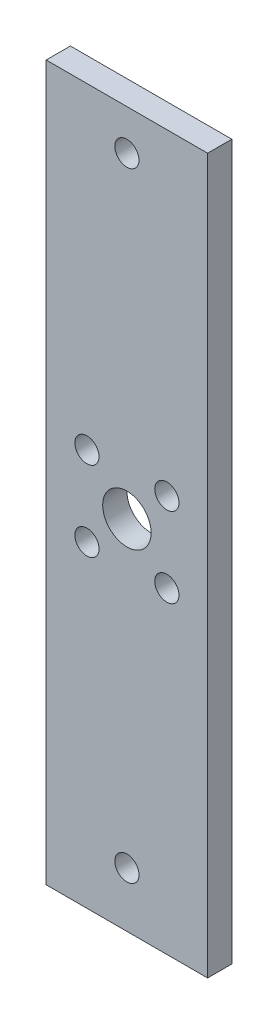
SolidWorks part; units mm, degrees
ref_plane "前视基准面" through (0, 0, 0) normal (0, 0, 1) x (1, 0, 0)
ref_plane "上视基准面" through (0, 0, 0) normal (0, 1, 0) x (1, 0, 0)
ref_plane "右视基准面" through (0, 0, 0) normal (1, 0, 0) x (0, 0, -1)
other "Configuration Table"
sketch "草图1" plane through (0, 0, 0) normal (0, 0, 1) x (1, 0, 0)
  line L1 (85.4719, -52.7604) -> (-85.4719, -52.7604)
  line L2 (85.4719, -52.7604) -> (85.4719, 52.7604)
  line L3 (85.4719, 52.7604) -> (-85.4719, 52.7604)
  line L4 (-85.4719, -52.7604) -> (-85.4719, 52.7604)
  line L5 (85.4719, -52.7604) -> (-85.4719, 52.7604) construction
  line L6 (85.4719, 52.7604) -> (-85.4719, -52.7604) construction
  point P0 (0, 0)
extrude "凸台-拉伸1" add sketch "草图1" along normal blind 3
sketch "草图2" plane through (0, 0, 0) normal (0, 0, -1) x (-1, 0, 0)
  circle A0 centre (7.0546, 5.7109) radius 1.5
  circle A1 centre (16.954, 5.7109) radius 1.5
  circle A2 centre (16.954, -4.1886) radius 1.5
  circle A3 centre (7.0546, -4.1886) radius 1.5
  circle A4 centre (12.0043, 0.7612) radius 3
sketch "草图3" plane through (0, 0, 3) normal (0, 0, 1) x (1, 0, 0)
  line L0 (-22.0043, -60.1388) -> (-22.0043, 59.8612) construction
  line L1 (-2.0043, -43.4888) -> (-22.0043, -43.4888)
  line L2 (-2.0043, -43.4888) -> (-2.0043, 45.0112)
  line L3 (-2.0043, 45.0112) -> (-22.0043, 45.0112)
  line L4 (-22.0043, -43.4888) -> (-22.0043, 45.0112)
  line L5 (-2.0043, -43.4888) -> (-22.0043, 45.0112) construction
  line L6 (-2.0043, 45.0112) -> (-22.0043, -43.4888) construction
  point P0 (-12.0043, 0.7612)
extrude "切除-拉伸1" cut sketch "草图3" against normal through all flip side to cut contours L2 L3 L4 L1
extrude "切除-拉伸2" cut sketch "草图2" against normal through all
sketch "草图4" plane through (0, 0, 0) normal (0, 0, -1) x (-1, 0, 0)
  circle A0 centre (12.0043, 40.0074) radius 1.5
  circle A1 centre (12.0043, -36.6851) radius 1.5
extrude "切除-拉伸3" cut sketch "草图4" against normal through all
